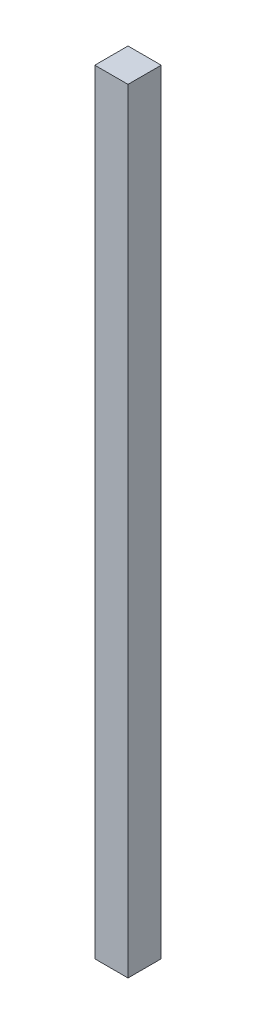
SolidWorks part; units mm, degrees
ref_plane "Plan de face" through (0, 0, 0) normal (0, 0, 1) x (1, 0, 0)
ref_plane "Plan de dessus" through (0, 0, 0) normal (0, 1, 0) x (1, 0, 0)
ref_plane "Plan de droite" through (0, 0, 0) normal (1, 0, 0) x (0, 0, -1)
sketch "Esquisse1" plane through (0, 0, 0) normal (0, 0, 1) x (1, 0, 0)
  line L1 (-73.6499, 111.4583) -> (-63.6499, 111.4583)
  line L2 (-73.6499, 111.4583) -> (-73.6499, -121.5417)
  line L3 (-73.6499, -121.5417) -> (-63.6499, -121.5417)
  line L4 (-63.6499, 111.4583) -> (-63.6499, -121.5417)
  dimension "D1" = 10
  dimension "D2" = 233
extrude "Boss.-Extru.1" add sketch "Esquisse1" along normal blind 10
equation "\"EpaisseurPlaque\"= 3"
equation "\"ProfondeurBoite\"=460"
equation "\"LongueurSyphon\"=170"
equation "\"LargeurSyphon\"=120"
equation "\"HauteurCoteDroit\"= 490"
equation "\"HauteurCoteGauche\"= 540"
equation "\"HauteurSolSyphon\"= 300"
equation "\"HauteurSyphon\"=\"HauteurCoteGauche\"-\"HauteurSolSyphon\""
equation "\"LargeurDroite\"=10"
equation "\"LargeurGauche\"=150"
equation "\"LargeurBoite\"= \"LargeurDroite\" + \"LargeurGauche\" + \"LargeurSyphon\""
equation "\"D2@Esquisse1\"=\"HauteurSyphon\" - 10 + 3"
